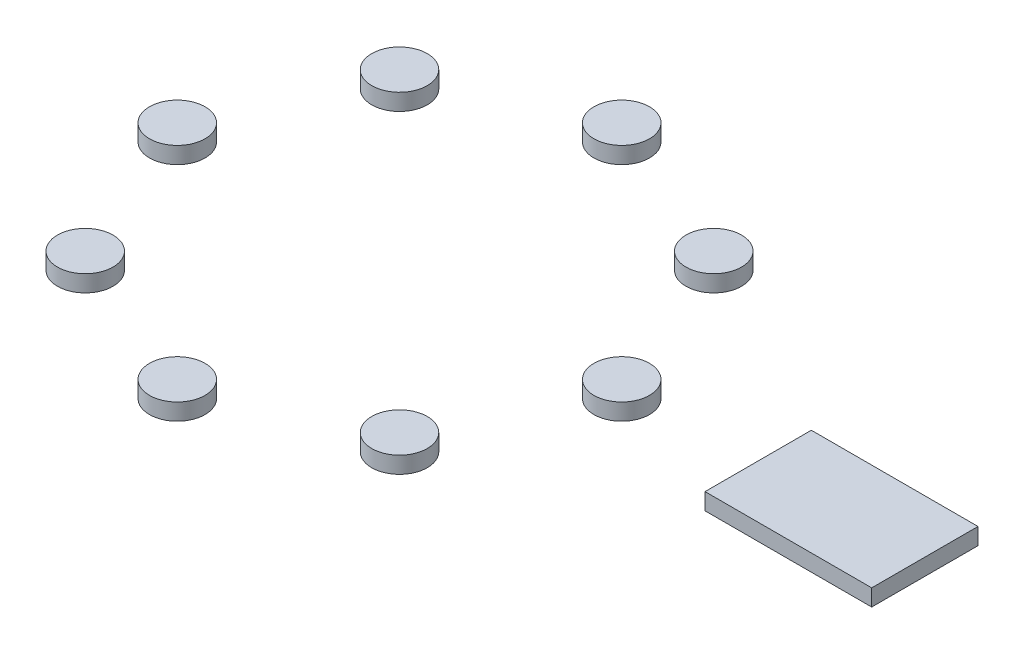
SolidWorks part; units mm, degrees
ref_plane "Front Plane" through (0, 0, 0) normal (0, 0, 1) x (1, 0, 0)
ref_plane "Top Plane" through (0, 0, 0) normal (0, 1, 0) x (1, 0, 0)
ref_plane "Right Plane" through (0, 0, 0) normal (1, 0, 0) x (0, 0, -1)
sketch "Sketch1" plane through (0, 0, 0) normal (0, 1, 0) x (1, 0, 0)
  line L0 (-37.5, 0) -> (-15, 0) construction
  line L7 (32.5, -5) -> (17.5, -5)
  line L8 (32.5, -5) -> (32.5, 4.5667)
  line L9 (32.5, 4.5667) -> (17.5, 4.5667)
  line L10 (17.5, -5) -> (17.5, 4.5667)
  line L11 (32.5, -5) -> (17.5, 4.5667) construction
  line L12 (32.5, 4.5667) -> (17.5, -5) construction
  circle A0 centre (-35, 0) radius 2.5
  circle A2 centre (-29.1421, 14.1421) radius 2.5
  circle A3 centre (-15, 20) radius 2.5
  circle A4 centre (-0.8579, 14.1421) radius 2.5
  circle A5 centre (5, 0) radius 2.5
  circle A6 centre (-0.8579, -14.1421) radius 2.5
  circle A7 centre (-15, -20) radius 2.5
  circle A8 centre (-29.1421, -14.1421) radius 2.5
  point P0 (0, 0)
  point P6 (25, -0.2166)
  dimension "D3" = 5
  dimension "D6" = 22.5
  dimension "D9" = 15
  dimension "D7" = 8
extrude "Boss-Extrude3" add sketch "Sketch1" along normal blind 1.5 contours A5 | A7 | A8 | A0 | L10 L7 L8 L9 | A2 | A3 | A4 | A6 region at (25, 0, 0.2166) region at (-35, 0, 0) region at (-29.1421, 0, -14.1421) region at (5, 0, 0) region at (-15, 0, 20) region at (-29.1421, 0, 14.1421)
